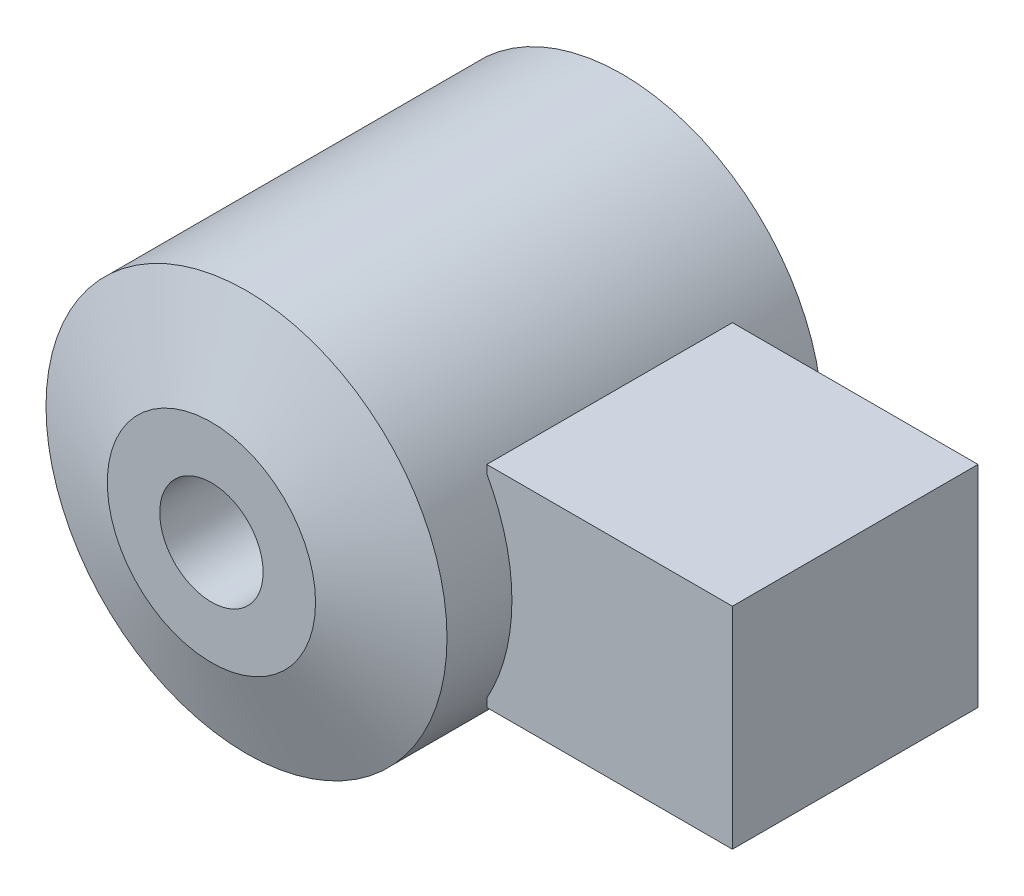
SolidWorks part; units mm, degrees
material "7075-T6 (SN)"
ref_plane "Front Plane" through (0, 0, 0) normal (0, 0, 1) x (1, 0, 0)
ref_plane "Top Plane" through (0, 0, 0) normal (0, 1, 0) x (1, 0, 0)
ref_plane "Right Plane" through (0, 0, 0) normal (1, 0, 0) x (0, 0, -1)
sketch "Sketch1" plane through (0, 0, 0) normal (0, 0, 1) x (1, 0, 0)
  circle A0 centre (0, 0) radius 5.715
  dimension "D1" = 11.43
extrude "Boss-Extrude1" add sketch "Sketch1" along normal blind 12.7
sketch "Sketch2" plane through (0, 0, 12.7) normal (0, 0, 1) x (1, 0, 0)
  circle A0 centre (0, 0) radius 1.4732
  dimension "D1" = 2.9464
extrude "Cut-Extrude1" cut sketch "Sketch2" against normal through all
chamfer "Chamfer1" distance 1 angle 70 1 edges at (5.715, 0, 12.7) first distance on face at (5.715, 0, 12.7)
chamfer "Chamfer3" distance 1 angle 70 1 edges at (5.715, 0, 0) first distance on face at (5.715, 0, 11.7)
ref_plane "Plane2" through (5, 0, 0) normal (1, 0, 0) x (0, 0, -1)
sketch "Sketch3" plane through (5, 0, 0) normal (1, 0, 0) x (0, 0, -1)
  line L0 (6.2865, 0) -> (-6.2865, 0) construction
  line L1 (-9.85, 3) -> (-2.85, 3)
  line L2 (-9.85, 3) -> (-9.85, -3)
  line L3 (-9.85, -3) -> (-2.85, -3)
  line L4 (-2.85, 3) -> (-2.85, -3)
  line L5 (-9.85, 3) -> (-2.85, -3) construction
  line L6 (-9.85, -3) -> (-2.85, 3) construction
  line L7 (0, 6.2865) -> (0, -6.2865) construction
  point P0 (-6.35, 0)
  dimension "D1" = 6.35
  dimension "D2" = 6
  dimension "D3" = 7
extrude "Boss-Extrude2" add sketch "Sketch3" along normal blind 7
equation "\"FrangiboltTotalDiameter\" = 0.450in"
equation "\"FrangiboltTotalLength\" = 0.500in"
equation "\"FrangiboltThruHoleDiameter\"= 0.116in"
equation "\"D1@Sketch1\"=\"FrangiboltTotalDiameter\""
equation "\"D1@Boss-Extrude1\"=\"FrangiboltTotalLength\""
equation "\"D1@Sketch2\"=\"FrangiboltThruHoleDiameter\""
equation "\"D1@Sketch3\"=\"FrangiboltTotalLength\"/2"
